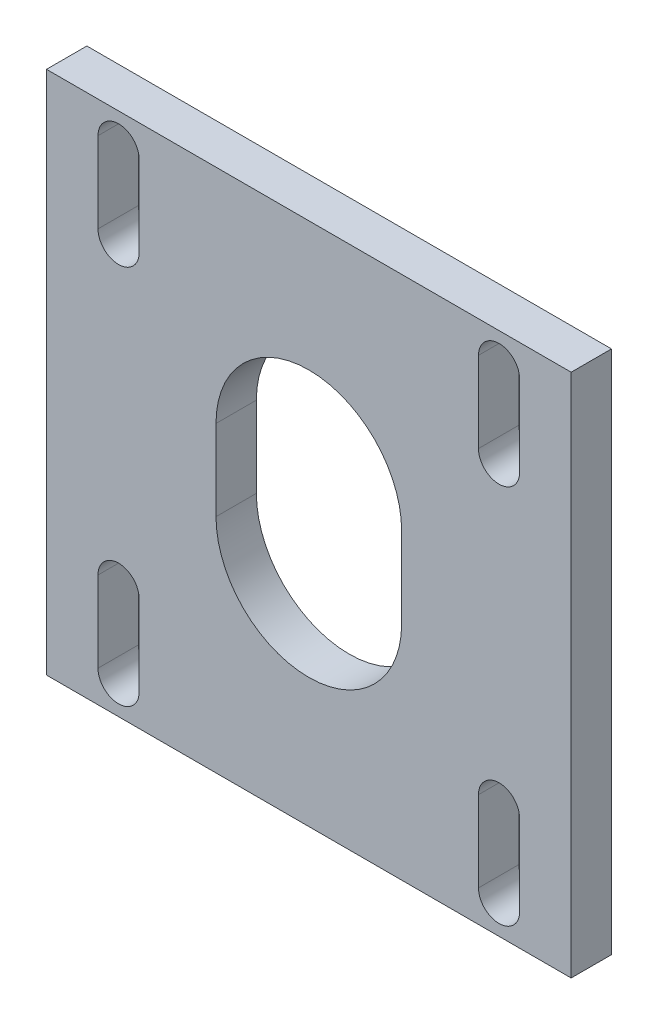
SolidWorks part; units mm, degrees
ref_plane "Front Plane" through (0, 0, 0) normal (0, 0, 1) x (1, 0, 0)
ref_plane "Top Plane" through (0, 0, 0) normal (0, 1, 0) x (1, 0, 0)
ref_plane "Right Plane" through (0, 0, 0) normal (1, 0, 0) x (0, 0, -1)
sketch "Sketch1" plane through (0, 0, 0) normal (0, 0, 1) x (1, 0, 0)
  line L2 (0, 0) -> (0, -65)
  line L3 (0, -65) -> (65, -65)
  line L9 (65, -65) -> (65, 0)
  line L10 (0, 0) -> (65, 0)
  line L11 (8.93, -8.93) -> (56.07, -8.93) construction
  line L12 (32.5, 0) -> (32.5, -65) construction
  line L13 (0, -32.5) -> (65, -32.5) construction
  line L14 (8.93, -3.93) -> (8.93, -13.93) construction
  line L15 (56.07, -56.07) -> (56.07, -8.93) construction
  line L16 (11.48, -3.93) -> (11.48, -13.93)
  line L17 (6.38, -3.93) -> (6.38, -13.93)
  line L18 (56.07, -3.93) -> (56.07, -13.93) construction
  line L19 (53.52, -3.93) -> (53.52, -13.93)
  line L20 (58.62, -3.93) -> (58.62, -13.93)
  line L21 (8.93, -61.07) -> (8.93, -51.07) construction
  line L22 (11.48, -61.07) -> (11.48, -51.07)
  line L23 (6.38, -61.07) -> (6.38, -51.07)
  line L24 (56.07, -61.07) -> (56.07, -51.07) construction
  line L25 (53.52, -61.07) -> (53.52, -51.07)
  line L26 (58.62, -61.07) -> (58.62, -51.07)
  arc A8 (11.48, -3.93) -> (6.38, -3.93) centre (8.93, -3.93) ccw
  arc A9 (6.38, -13.93) -> (11.48, -13.93) centre (8.93, -13.93) ccw
  arc A10 (53.52, -3.93) -> (58.62, -3.93) centre (56.07, -3.93) cw
  arc A11 (58.62, -13.93) -> (53.52, -13.93) centre (56.07, -13.93) cw
  arc A12 (11.48, -61.07) -> (6.38, -61.07) centre (8.93, -61.07) cw
  arc A13 (6.38, -51.07) -> (11.48, -51.07) centre (8.93, -51.07) cw
  arc A14 (53.52, -61.07) -> (58.62, -61.07) centre (56.07, -61.07) ccw
  arc A15 (58.62, -51.07) -> (53.52, -51.07) centre (56.07, -51.07) ccw
  point P16 (32.5, -8.93)
  point P17 (56.07, -32.5)
  point P20 (8.93, -8.93)
  point P21 (65, -65)
  point P26 (0, 0)
  point P28 (0, 0)
  point P29 (65, 0)
  point P31 (56.07, -8.93)
  point P37 (8.93, -56.07)
  point P44 (56.07, -56.07)
  dimension "D6" = 10
  dimension "D1" = 65
  dimension "D2" = 65
extrude "Boss-Extrude1" add sketch "Sketch1" along normal blind 5
sketch "Sketch2" plane through (0, 0, 5) normal (0, 0, 1) x (1, 0, 0)
  line L3 (32.5, -27.5) -> (32.5, -37.5) construction
  line L4 (44, -27.5) -> (44, -37.5)
  line L5 (21, -27.5) -> (21, -37.5)
  line L6 (0, 0) -> (0, -65) construction
  line L7 (65, 0) -> (0, 0) construction
  arc A1 (44, -27.5) -> (21, -27.5) centre (32.5, -27.5) ccw
  arc A2 (21, -37.5) -> (44, -37.5) centre (32.5, -37.5) ccw
  point P5 (32.5, -32.5)
  point P7 (0, -32.5)
  point P10 (32.5, 0)
  dimension "D1" = 10
  dimension "D2" = 11.5
extrude "Cut-Extrude2" cut sketch "Sketch2" against normal up to next
